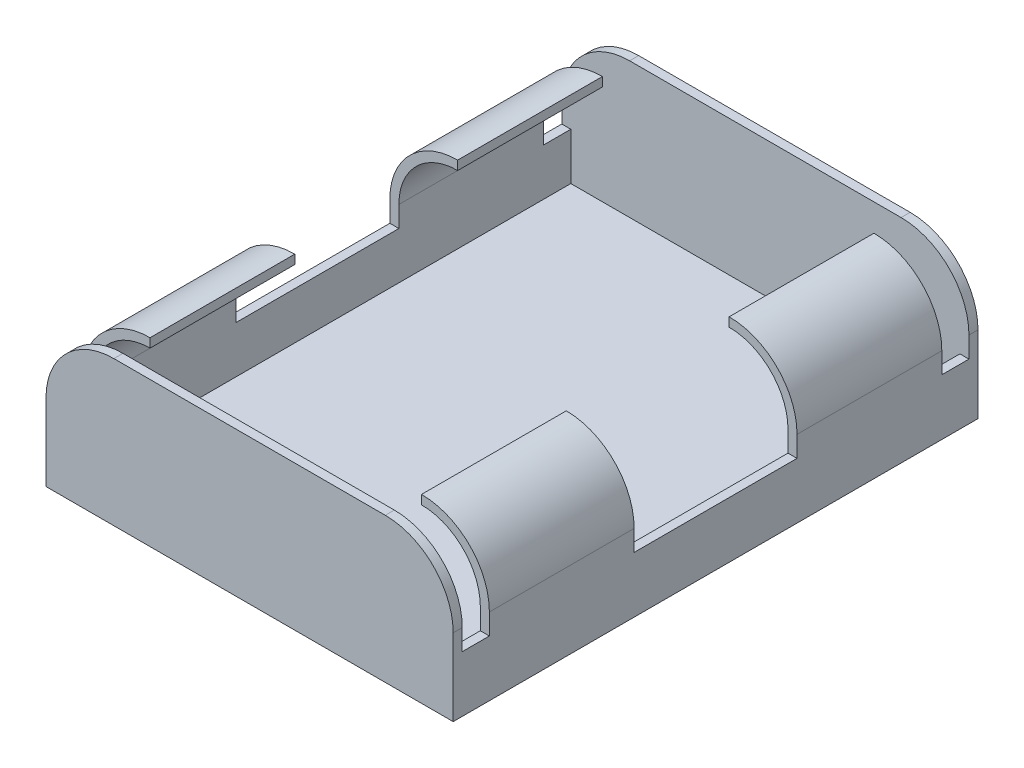
SolidWorks part; units mm, degrees
ref_plane "Front Plane" through (0, 0, 0) normal (0, 0, 1) x (1, 0, 0)
ref_plane "Top Plane" through (0, 0, 0) normal (0, 1, 0) x (1, 0, 0)
ref_plane "Right Plane" through (0, 0, 0) normal (1, 0, 0) x (0, 0, -1)
sketch "Sketch1" plane through (0, 0, 0) normal (0, 1, 0) x (1, 0, 0)
  line L0 (0, 29) -> (0, 0) construction
  line L1 (-22.5, 29) -> (22.5, 29)
  line L2 (-22.5, 29) -> (-22.5, -29)
  line L3 (-22.5, -29) -> (22.5, -29)
  line L4 (22.5, 29) -> (22.5, -29)
  line L5 (0, 0) -> (0, -29) construction
  dimension "D1" = 45
  dimension "D2" = 58
extrude "Boss-Extrude1" add sketch "Sketch1" along normal mid plane 16
fillet "Fillet1" radius 7.5 2 edges at (-22.5, 8, 0) (22.5, 8, 0)
shell "Shell1" thickness 1 removed face at (0, 8, 0)
sketch "Sketch2" plane through (22.5, 0, 0) normal (1, 0, 0) x (0, 0, -1)
  line L0 (0, -1.8) -> (0, 0) construction
  line L1 (-9, 13.2) -> (9, 13.2)
  line L2 (-9, 13.2) -> (-9, -1.8)
  line L3 (-9, -1.8) -> (9, -1.8)
  line L4 (9, 13.2) -> (9, -1.8)
  line L5 (-28, 13.2) -> (-25, 13.2)
  line L6 (-28, 13.2) -> (-28, -1.8)
  line L7 (-28, -1.8) -> (-25, -1.8)
  line L8 (-25, 13.2) -> (-25, -1.8)
  line L9 (28, 13.2) -> (25, 13.2)
  line L10 (28, 13.2) -> (28, -1.8)
  line L11 (28, -1.8) -> (25, -1.8)
  line L12 (25, 13.2) -> (25, -1.8)
  line L13 (-25, -1.8) -> (-9, -1.8) construction
  line L14 (9, -1.8) -> (25, -1.8) construction
  line L15 (29, 0.5) -> (29, -8) construction
  line L16 (-29, -8) -> (29, -8) construction
  dimension "D1" = 1
  dimension "D2" = 3
  dimension "D3" = 18
  dimension "D4" = 6.2
  dimension "D5" = 15
extrude "Cut-Extrude1" cut sketch "Sketch2" against normal through all
sketch "Sketch3" plane through (0, 0, -29) normal (0, 0, -1) x (-1, 0, 0)
  line L0 (-22.5, -8) -> (22.5, -8) construction
  line L1 (22.5, 0.5) -> (22.5, -8) construction
  arc A0 (18.941, -7) -> (18.941, -6) centre (19.5, -6.5) ccw
  arc A1 (18.941, -6) -> (18.941, -7) centre (18.382, -6.5) ccw
  dimension "D1" = 1.5
  dimension "D2" = 1.5
  dimension "D3" = 3
  dimension "D4" = 1
extrude "Boss-Extrude2" add sketch "Sketch3" along normal blind 10
